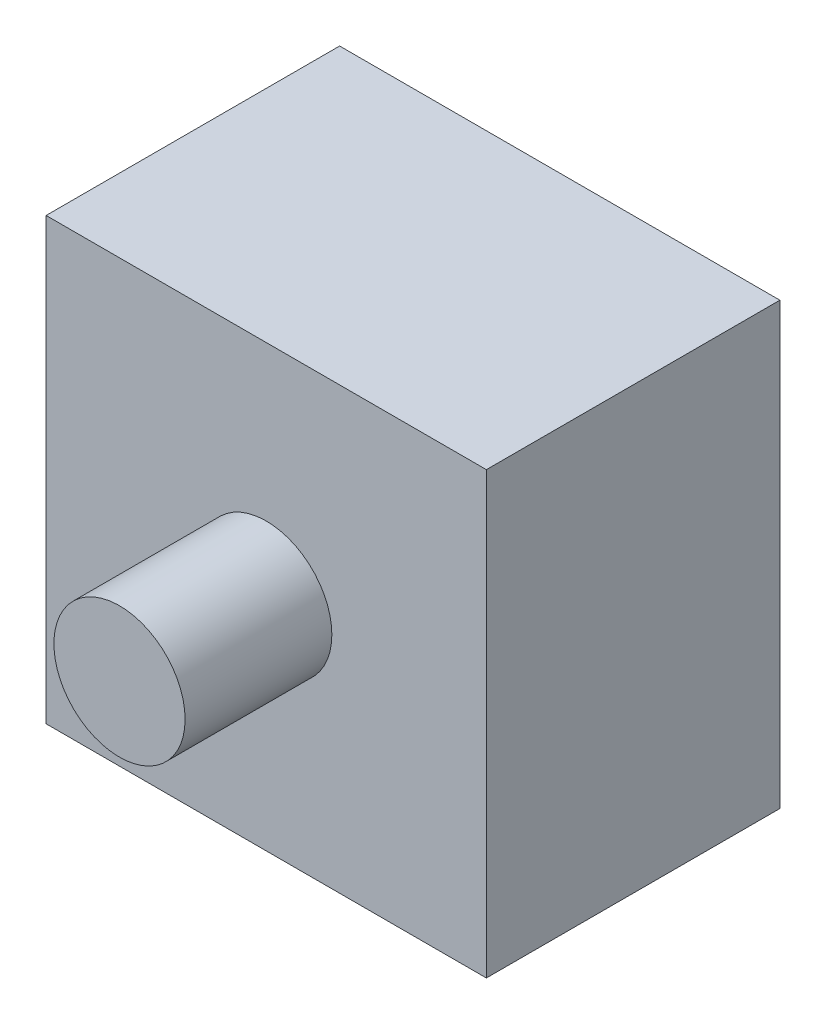
SolidWorks part; units mm, degrees
ref_plane "Front Plane" through (0, 0, 0) normal (0, 0, 1) x (1, 0, 0)
ref_plane "Top Plane" through (0, 0, 0) normal (0, 1, 0) x (1, 0, 0)
ref_plane "Right Plane" through (0, 0, 0) normal (1, 0, 0) x (0, 0, -1)
sketch "Sketch1" plane through (0, 0, 0) normal (0, 0, 1) x (1, 0, 0)
  line L1 (-1.5, -1.5) -> (1.5, -1.5)
  line L2 (-1.5, -1.5) -> (-1.5, 1.5)
  line L3 (-1.5, 1.5) -> (1.5, 1.5)
  line L4 (1.5, -1.5) -> (1.5, 1.5)
  line L5 (-1.5, -1.5) -> (1.5, 1.5) construction
  line L6 (-1.5, 1.5) -> (1.5, -1.5) construction
  point P0 (0, 0)
  dimension "D1" = 3
  dimension "D2" = 3
extrude "Boss-Extrude1" add sketch "Sketch1" along normal blind 2
sketch "Sketch2" plane through (0, 0, 2) normal (0, 0, 1) x (1, 0, 0)
  circle A0 centre (0, 0) radius 0.447
extrude "Boss-Extrude2" add sketch "Sketch2" along normal blind 1
other "CPoint1" parameters "Diameter"=25.4, "StubLength"=38.1
ref_axis "Axis1" through (0, 0, 13) along (0, 0, -1)
